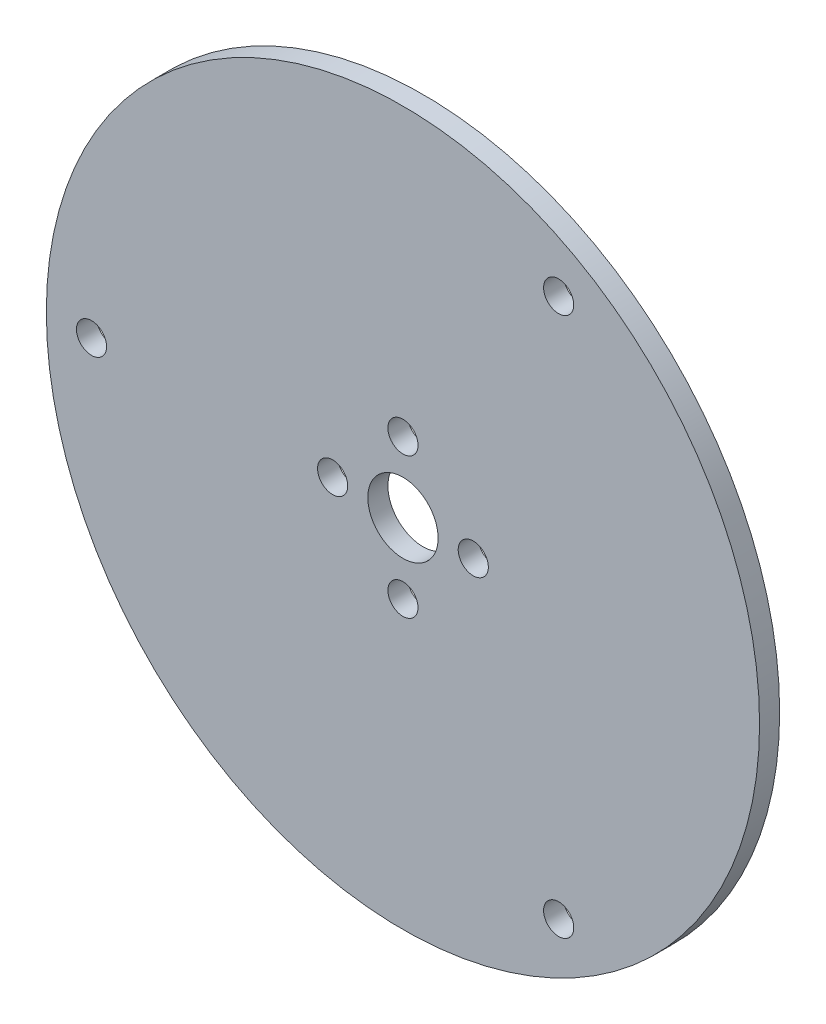
SolidWorks part; units mm, degrees
ref_plane "前视基准面" through (0, 0, 0) normal (0, 0, 1) x (1, 0, 0)
ref_plane "上视基准面" through (0, 0, 0) normal (0, 1, 0) x (1, 0, 0)
ref_plane "右视基准面" through (0, 0, 0) normal (1, 0, 0) x (0, 0, -1)
sketch "草图1" plane through (0, 0, 0) normal (0, 0, 1) x (1, 0, 0)
  circle A0 centre (0, 0) radius 35.5
extrude "凸台-拉伸1" add sketch "草图1" along normal blind 2
sketch "草图2" plane through (0, 0, 2) normal (0, 0, 1) x (1, 0, 0)
  circle A0 centre (0, 0) radius 3.5
extrude "切除-拉伸1" cut sketch "草图2" against normal blind 2
sketch "草图3" plane through (0, 0, 2) normal (0, 0, 1) x (1, 0, 0)
  circle A0 centre (0, 7) radius 1.5
  circle A1 centre (7, 0) radius 1.5
  circle A2 centre (0, -7) radius 1.5
  circle A3 centre (-7, 0) radius 1.5
  point P12 (0, 0)
  dimension "D1" = 4
extrude "切除-拉伸2" cut sketch "草图3" against normal blind 2
sketch "草图5" plane through (0, 0, 2) normal (0, 0, 1) x (1, 0, 0)
  circle A0 centre (-31, 0) radius 1.5
  circle A1 centre (15.5, 26.8468) radius 1.5
  circle A2 centre (15.5, -26.8468) radius 1.5
  point P10 (0, 0)
  dimension "D1" = 3
extrude "切除-拉伸3" cut sketch "草图5" against normal blind 2
